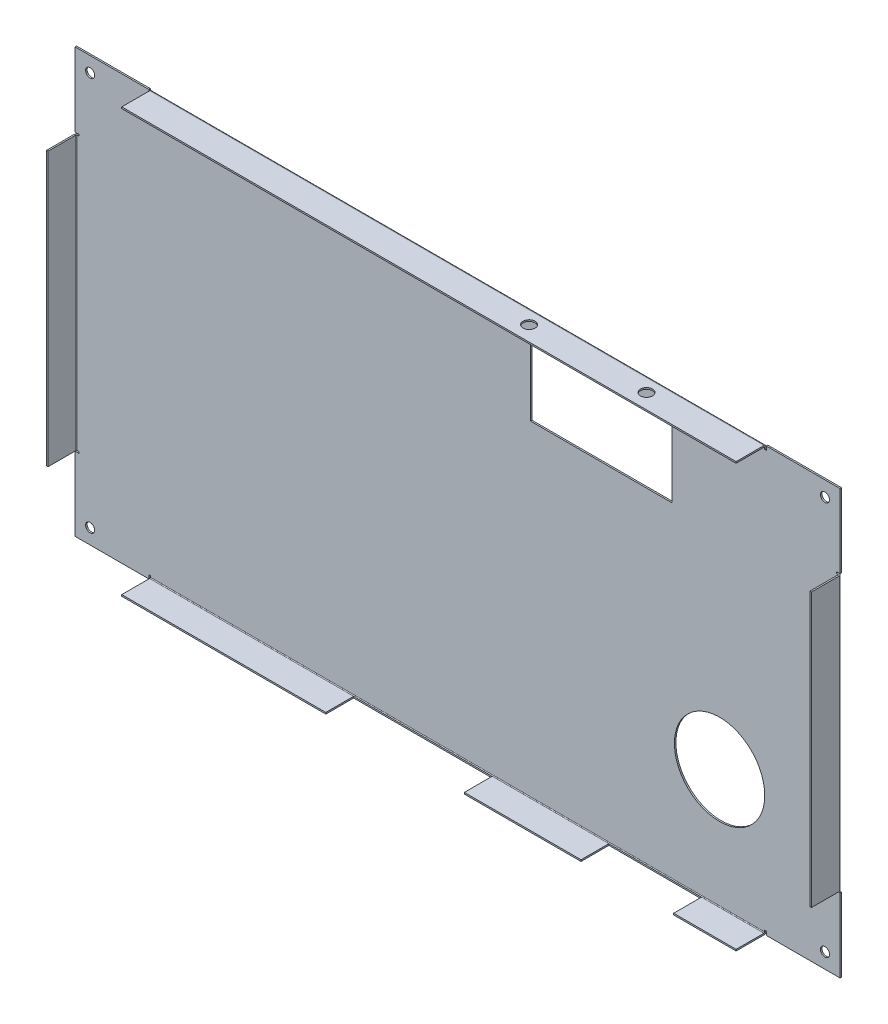
SolidWorks part; units mm, degrees
note: The reader was unsure of these and kept them because the rebuilt part matched: thickness of "基体-法兰1", "边线-法兰1", "边线-法兰2", "边线-法兰3", "边线-法兰4", "钣金1", "钣金2", "钣金3", "钣金4", "钣金5", "钣金6", "钣金7"; flange length of "边线-法兰1", "边线-法兰2", "边线-法兰3", "边线-法兰4".
ref_plane "前视基准面" through (0, 0, 0) normal (0, 0, 1) x (1, 0, 0)
ref_plane "上视基准面" through (0, 0, 0) normal (0, 1, 0) x (1, 0, 0)
ref_plane "右视基准面" through (0, 0, 0) normal (1, 0, 0) x (0, 0, -1)
sketch "草图1" plane through (0, 0, 0) normal (0, 0, 1) x (1, 0, 0)
  line L1 (-254, -140.75) -> (254, -140.75)
  line L2 (-254, -140.75) -> (-254, 140.75)
  line L3 (-254, 140.75) -> (254, 140.75)
  line L4 (254, -140.75) -> (254, 140.75)
  line L5 (-254, -140.75) -> (254, 140.75) construction
  line L6 (-254, 140.75) -> (254, -140.75) construction
  line L7 (48.5, 122.75) -> (142.5, 122.75)
  line L8 (48.5, 122.75) -> (48.5, 76.75)
  line L9 (48.5, 76.75) -> (142.5, 76.75)
  line L10 (142.5, 122.75) -> (142.5, 76.75)
  circle A0 centre (-244, 130.75) radius 3
  circle A1 centre (-244, -130.75) radius 3
  circle A2 centre (244, 130.75) radius 3
  circle A3 centre (244, -130.75) radius 3
  circle A4 centre (174, -60.75) radius 30
  point P0 (0, 0)
  dimension "D11" = 6
  dimension "D14" = 60
  dimension "D1" = 508
  dimension "D2" = 281.5
  dimension "D3" = 10
  dimension "D4" = 10
  dimension "D5" = 10
  dimension "D6" = 10
  dimension "D7" = 10
  dimension "D8" = 10
  dimension "D9" = 10
  dimension "D10" = 10
  dimension "D12" = 80
  dimension "D13" = 80
  dimension "D15" = 46
  dimension "D16" = 94
  dimension "D17" = 64
  dimension "D18" = 111.5
base flange "基体-法兰1" sketch "草图1" thickness 1 reverse thickness direction no parameters "D1"=0.5
edge flange "边线-法兰1" sketch "草图8" flange angle 90 flange length 20 flange position material inside bend radius 0.5 thickness 1 relief rectangular parameters "D6"=10
sketch "草图8" plane through (0, 140.75, 0) normal (0, 1, 0) x (-1, 0, 0)
  line L2 (-204, 0) -> (-204, 19)
  line L3 (-204, 19) -> (204, 19)
  line L4 (204, 19) -> (204, 0)
  line L5 (-254, 0) -> (254, 0) construction
  line L6 (-204, 0) -> (204, 0)
  line L7 (-254, -1) -> (-254, 0) construction
  line L8 (254, -1) -> (254, 0) construction
  dimension "D1" = 50
  dimension "D2" = 50
bend "边线折弯1" bend radius 0.5 bend angle 90 parameters "D5"=1
edge flange "边线-法兰2" sketch "草图11" flange angle 90 flange length 20 flange position material inside bend radius 0.5 thickness 1 relief rectangular parameters "D6"=10
sketch "草图11" plane through (0, -140.75, 0) normal (0, -1, 0) x (1, 0, 0)
  line L2 (-204, 0) -> (-204, 19)
  line L3 (-204, 19) -> (204, 19)
  line L4 (204, 19) -> (204, 0)
  line L5 (-254, 0) -> (254, 0) construction
  line L6 (-204, 0) -> (204, 0)
  line L7 (254, -1) -> (254, 0) construction
  line L8 (-254, -1) -> (-254, 0) construction
  dimension "D1" = 50
  dimension "D2" = 50
bend "边线折弯2" bend radius 0.5 bend angle 90 parameters "D5"=2
edge flange "边线-法兰3" sketch "草图14" flange angle 90 flange length 20 flange position material inside bend radius 0.5 thickness 1 relief rectangular parameters "D6"=10
sketch "草图14" plane through (254, 0, 0) normal (1, 0, 0) x (0, 1, 0)
  line L2 (-90.75, 0) -> (-90.75, 19)
  line L3 (-90.75, 19) -> (90.75, 19)
  line L4 (90.75, 19) -> (90.75, 0)
  line L5 (-140.75, 0) -> (140.75, 0) construction
  line L6 (-90.75, 0) -> (90.75, 0)
  line L7 (-140.75, -1) -> (-140.75, 0) construction
  line L8 (140.75, -1) -> (140.75, 0) construction
  dimension "D1" = 50
  dimension "D2" = 50
bend "边线折弯3" bend radius 0.5 bend angle 90 parameters "D5"=3
edge flange "边线-法兰4" sketch "草图17" flange angle 90 flange length 20 flange position material inside bend radius 0.5 thickness 1 relief rectangular parameters "D6"=10
sketch "草图17" plane through (-254, 0, 0) normal (-1, 0, 0) x (0, -1, 0)
  line L2 (-90.75, 0) -> (-90.75, 19)
  line L3 (-90.75, 19) -> (90.75, 19)
  line L4 (90.75, 19) -> (90.75, 0)
  line L5 (-140.75, 0) -> (140.75, 0) construction
  line L6 (-90.75, 0) -> (90.75, 0)
  line L7 (140.75, -1) -> (140.75, 0) construction
  line L8 (-140.75, -1) -> (-140.75, 0) construction
  dimension "D1" = 50
  dimension "D2" = 50
bend "边线折弯4" bend radius 0.5 bend angle 90 parameters "D5"=4
sketch "草图18" plane through (0, 139.75, 0) normal (0, -1, 0) x (-1, 0, 0)
  circle A0 centre (-134.5, -9) radius 4
  circle A1 centre (-56.5, -9) radius 4
  dimension "D1" = 8
extrude "切除-拉伸1" cut sketch "草图18" against normal through all normal cut yes
sketch "草图19" plane through (0, -139.75, 0) normal (0, 1, 0) x (1, 0, 0)
  line L0 (204, -19) -> (-204, -19) construction
  line L1 (-68.5, -19) -> (23.5, -19)
  line L2 (-68.5, -19) -> (-68.5, -0.5)
  line L3 (-68.5, -0.5) -> (23.5, -0.5)
  line L4 (23.5, -19) -> (23.5, -0.5)
  line L5 (-58.5, -2) -> (-58.5, -64) construction
  line L6 (101, -19) -> (162.5, -19)
  line L7 (101, -19) -> (101, -0.5)
  line L8 (101, -0.5) -> (162.5, -0.5)
  line L9 (162.5, -19) -> (162.5, -0.5)
  line L10 (13.5, -25.5) -> (13.5, -2) construction
  line L11 (111, -2) -> (111, -25.5) construction
  line L12 (152.5, -24) -> (152.5, -2) construction
  line L13 (-204, -0.5) -> (204, -0.5) construction
  dimension "D1" = 10
  dimension "D2" = 10
  dimension "D3" = 10
  dimension "D4" = 10
extrude "切除-拉伸2" cut sketch "草图19" against normal through all normal cut yes
sketch "折弯-线1" plane through (0, 0, 0) normal (0, 1, 0) x (1, 0, 0)
sketch "边界框1" plane through (0, 0, 0) normal (0, 1, 0) x (1, 0, 0)
sheet metal parameters "钣金1" thickness 1 parameters "D1"=0.5
flat pattern "平板型式1" [suppressed]
sketch "折弯-线2" plane through (0, 0, 0) normal (0, 1, 0) x (1, 0, 0)
sketch "边界框2" [suppressed] plane through (0, 0, 0) normal (0, 1, 0) x (1, 0, 0)
sheet metal parameters "钣金2" thickness 1 parameters "D1"=0.5, "D7"=0.8
flat pattern "平板型式1" [suppressed]
sketch "折弯-线2" plane through (0, 0, 0) normal (0, 1, 0) x (1, 0, 0)
sketch "边界框2" [suppressed] plane through (0, 0, 0) normal (0, 1, 0) x (1, 0, 0)
bend of the flat pattern "展开-<边线折弯1>1"
sheet metal parameters "钣金3" thickness 1 parameters "D1"=0.5, "D7"=0.8
flat pattern "平板型式1" [suppressed]
sketch "折弯-线2" plane through (0, 0, 0) normal (0, 1, 0) x (1, 0, 0)
sketch "边界框2" [suppressed] plane through (0, 0, 0) normal (0, 1, 0) x (1, 0, 0)
bend of the flat pattern "展开-<边线折弯1>1"
bend of the flat pattern "展开-<边线折弯2>1"
sheet metal parameters "钣金4" thickness 1 parameters "D1"=0.5, "D7"=0.8
flat pattern "平板型式1" [suppressed]
sketch "折弯-线2" plane through (0, 0, 0) normal (0, 1, 0) x (1, 0, 0)
sketch "边界框2" [suppressed] plane through (0, 0, 0) normal (0, 1, 0) x (1, 0, 0)
bend of the flat pattern "展开-<边线折弯1>1"
bend of the flat pattern "展开-<边线折弯2>1"
bend of the flat pattern "展开-<边线折弯3>1"
sheet metal parameters "钣金5" thickness 1 parameters "D1"=0.5, "D7"=0.8
flat pattern "平板型式1" [suppressed]
sketch "折弯-线2" plane through (0, 0, 0) normal (0, 1, 0) x (1, 0, 0)
sketch "边界框2" [suppressed] plane through (0, 0, 0) normal (0, 1, 0) x (1, 0, 0)
bend of the flat pattern "展开-<边线折弯1>1"
bend of the flat pattern "展开-<边线折弯2>1"
bend of the flat pattern "展开-<边线折弯3>1"
bend of the flat pattern "展开-<边线折弯4>1"
sheet metal parameters "钣金6" thickness 1 parameters "D1"=0.5, "D7"=0.8
flat pattern "平板型式1" [suppressed]
sketch "折弯-线2" plane through (0, 0, 0) normal (0, 1, 0) x (1, 0, 0)
sketch "边界框2" [suppressed] plane through (0, 0, 0) normal (0, 1, 0) x (1, 0, 0)
bend of the flat pattern "展开-<边线折弯1>1"
bend of the flat pattern "展开-<边线折弯2>1"
bend of the flat pattern "展开-<边线折弯3>1"
bend of the flat pattern "展开-<边线折弯4>1"
sheet metal parameters "钣金7" thickness 1 parameters "D1"=0.5, "D7"=0.8
flat pattern "平板型式1" [suppressed]
sketch "折弯-线2" plane through (0, 0, 0) normal (0, 1, 0) x (1, 0, 0)
sketch "边界框2" [suppressed] plane through (0, 0, 0) normal (0, 1, 0) x (1, 0, 0)
bend of the flat pattern "展开-<边线折弯1>1"
bend of the flat pattern "展开-<边线折弯2>1"
bend of the flat pattern "展开-<边线折弯3>1"
bend of the flat pattern "展开-<边线折弯4>1"
